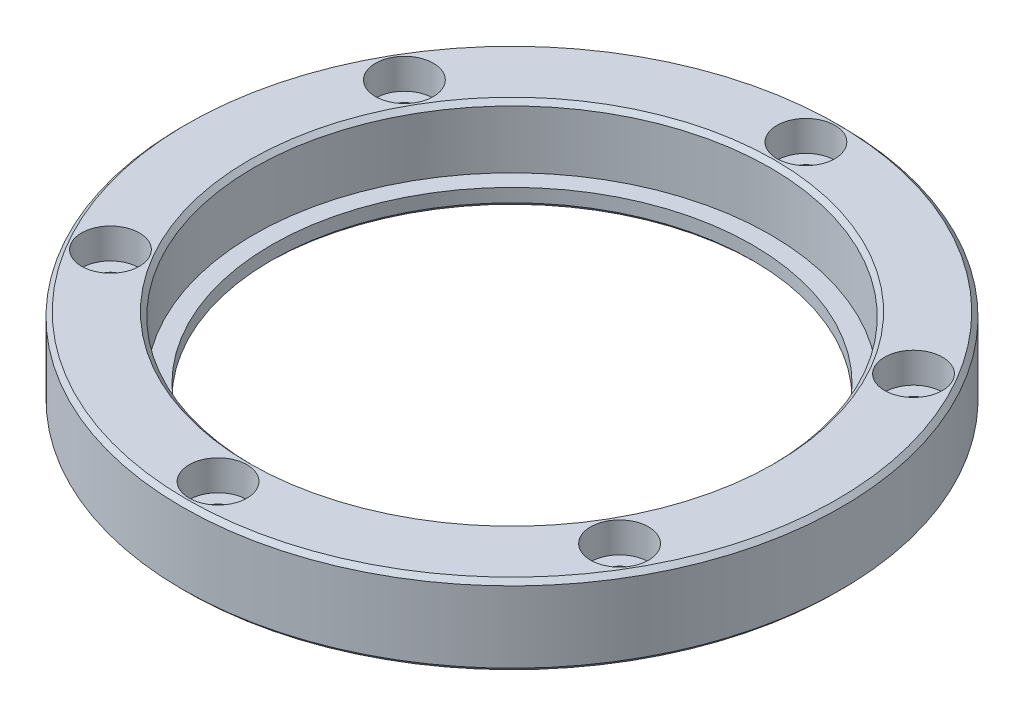
SolidWorks part; units mm, degrees
ref_plane "Ebene vorne" through (0, 0, 0) normal (0, 0, 1) x (1, 0, 0)
ref_plane "Ebene oben" through (0, 0, 0) normal (0, 1, 0) x (1, 0, 0)
ref_plane "Ebene rechts" through (0, 0, 0) normal (1, 0, 0) x (0, 0, -1)
sketch "Sketch1" plane through (0, 0, 0) normal (0, 0, 1) x (1, 0, 0)
  line L0 (0, 0) -> (0, 50) construction
  line L1 (27, 0) -> (37, 0)
  line L2 (37, 0) -> (37, 9)
  line L3 (37, 9) -> (29, 9)
  line L4 (29, 9) -> (29, 2)
  line L5 (29, 2) -> (27, 2)
  line L6 (27, 2) -> (27, 0)
  dimension "D1" = 50
  dimension "D2" = 2
  dimension "D3" = 8
  dimension "D4" = 7
  dimension "D5" = 2
  dimension "D6" = 58
revolve "Revolve1" add sketch "Sketch1" angle 360 about L0
hole_wizard "CBORE for M3 Hex Socket Head Cap Screw1" positions "Sketch3" profile "Sketch4" counterbore size "M3" standard "DIN" end condition through all
sketch "Sketch3" plane through (0, 9, 0) normal (0, 1, 0) x (1, 0, 0)
  line L0 (0, -29) -> (0, -37) construction
  circle A0 centre (0, 0) radius 29 construction
  circle A1 centre (0, 0) radius 29 construction
  circle A2 centre (0, 0) radius 37 construction
  point P10 (0, -33)
  point P17 (-28.5788, -16.5)
  point P18 (-28.5788, 16.5)
  point P19 (0, 33)
  point P20 (28.5788, 16.5)
  point P21 (28.5788, -16.5)
  dimension "D1" = 6
sketch "Sketch4" plane through (28.5788, 9, 16.5) normal (1, 0, 0) x (0, 0, 1)
  line L0 (0, 0) -> (0, 9)
  line L1 (0, 9) -> (1.7, 9)
  line L3 (1.7, 9) -> (1.7, 3.4)
  line L4 (1.7, 3.4) -> (3.25, 3.4)
  line L5 (3.25, 3.4) -> (3.25, 0)
  line L7 (3.25, 0) -> (0, 0)
  line L11 (0, -6.35) -> (0, 107.95) construction
  dimension "Thru Hole Dia." = 3.4
  dimension "Thru Hole Depth" = 9
  dimension "C'Bore Dia." = 6.5
  dimension "C'Bore Depth" = 3.4
chamfer "0,5mm Chamfer1" distance 0.5 angle 45 4 edges at (0, 0, -27) (0, 0, -37) (0, 9, -37) (0, 9, -29)
